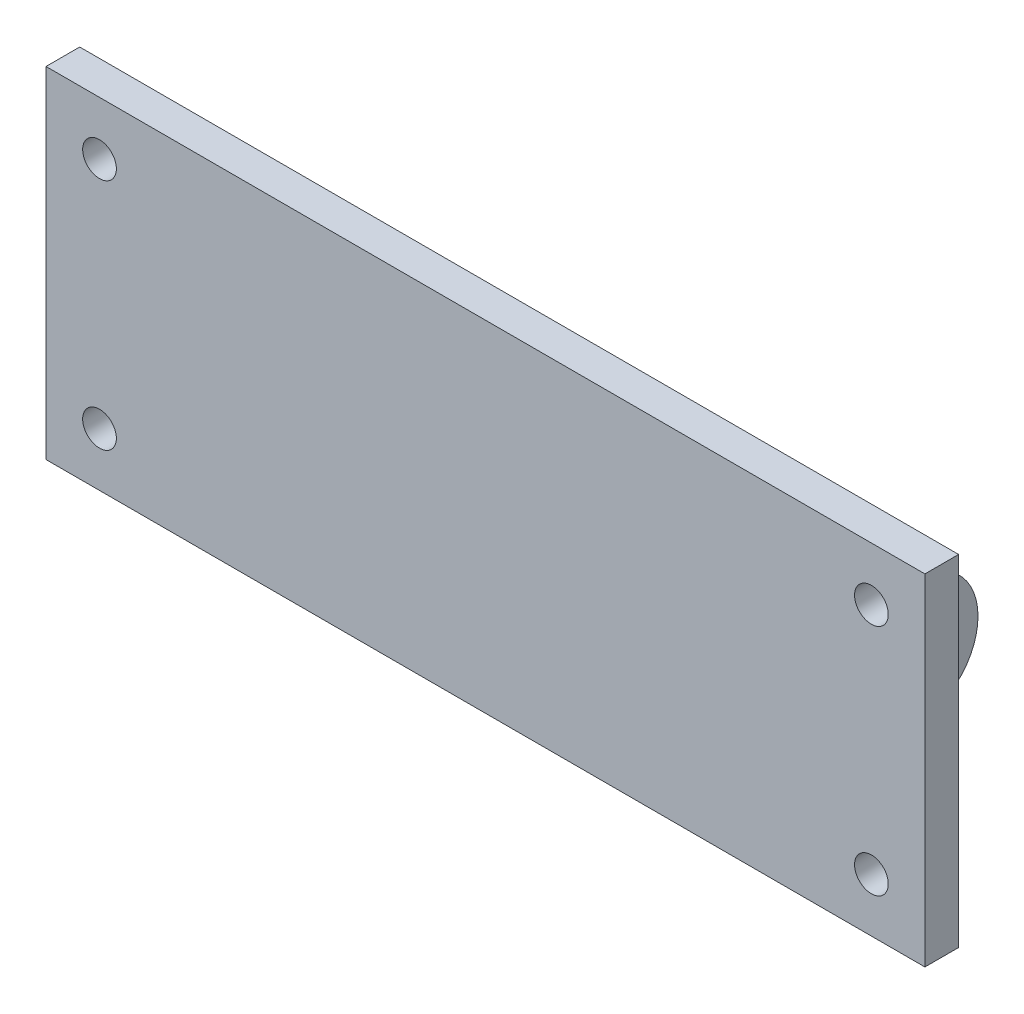
SolidWorks part; units mm, degrees
ref_plane "Front Plane" through (0, 0, 0) normal (0, 0, 1) x (1, 0, 0)
ref_plane "Top Plane" through (0, 0, 0) normal (0, 1, 0) x (1, 0, 0)
ref_plane "Right Plane" through (0, 0, 0) normal (1, 0, 0) x (0, 0, -1)
sketch "Sketch1" plane through (0, 0, 0) normal (0, 0, 1) x (1, 0, 0)
  line L0 (-57.0556, -260.4467) -> (-37.0556, -260.4467)
  line L5 (-57.0556, -260.4467) -> (-57.0556, -290.4467)
  line L6 (-57.0556, -290.4467) -> (-37.0556, -290.4467)
  line L11 (-37.0556, -260.4467) -> (-37.0556, -290.4467)
  line L12 (-57.0556, -260.4467) -> (-37.0556, -290.4467) construction
  line L13 (-57.0556, -290.4467) -> (-37.0556, -260.4467) construction
  line L14 (80.7444, -260.4467) -> (100.7444, -260.4467)
  line L15 (80.7444, -260.4467) -> (80.7444, -290.4467)
  line L16 (80.7444, -290.4467) -> (100.7444, -290.4467)
  line L17 (100.7444, -260.4467) -> (100.7444, -290.4467)
  line L18 (80.7444, -260.4467) -> (100.7444, -290.4467) construction
  line L19 (80.7444, -290.4467) -> (100.7444, -260.4467) construction
  line L21 (126.1444, -235.0467) -> (-82.4556, -235.0467)
  line L22 (126.1444, -235.0467) -> (126.1444, -315.8467)
  line L23 (126.1444, -315.8467) -> (-82.4556, -315.8467)
  line L24 (-82.4556, -235.0467) -> (-82.4556, -315.8467)
  line L25 (126.1444, -235.0467) -> (-82.4556, -315.8467) construction
  line L26 (126.1444, -315.8467) -> (-82.4556, -235.0467) construction
  circle A0 centre (113.4444, -247.7467) radius 4
  circle A1 centre (-69.7556, -303.1467) radius 4
  circle A3 centre (113.4444, -303.1467) radius 4
  circle A4 centre (-69.7556, -247.7467) radius 4
  point P0 (-47.0556, -275.4467)
  point P5 (90.7444, -275.4467)
  point P10 (21.8444, -275.4467)
  dimension "D7" = 8
  dimension "D8" = 12.7
  dimension "D10" = 12.7
  dimension "D11" = 25.4
  dimension "D14" = 8
  dimension "D15" = 12.7
  dimension "D17" = 8
  dimension "D18" = 8
  dimension "D19" = 12.7
  dimension "D20" = 12.7
  dimension "D21" = 12.7
  dimension "D22" = 12.7
  dimension "D1" = 20
  dimension "D2" = 30
  dimension "D3" = 20
  dimension "D4" = 30
  dimension "D5" = 117.8
  dimension "D6" = 0
  dimension "D9" = 25.4
  dimension "D12" = 25.4
  dimension "D13" = 25.4
  dimension "D16" = 12.7
extrude "Boss-Extrude1" add sketch "Sketch1" along normal blind 8 contours L17 L14 L15 L16 | L11 L0 L5 L6 | L21 L24 L23 L22 A3 A4 A1 A0 L14 L17 L16 L15 L0 L11 L6 L5 region at (-47.0556, -275.4467, 0) region at (90.7444, -275.4467, 0) region at (21.8444, -275.4467, 0)
extrude "Boss-Extrude2" add sketch "Sketch1<3>" against normal blind 30 contours L17 L14 L15 L16 | L11 L0 L5 L6 region at (-47.0556, -275.4467, 0) region at (90.7444, -275.4467, 0)
sketch "Sketch1<3>" plane through (0, 0, 0) normal (0, 0, 1) x (1, 0, 0) same geometry as "Sketch1"
fillet "Fillet1" radius 5 4 edges at (-47.0556, -260.4467, 0) (-47.0556, -290.4467, 0) (90.7444, -290.4467, 0) (90.7444, -260.4467, 0)
fillet "Fillet2" radius 15 4 edges at (90.7444, -260.4467, -30) (90.7444, -290.4467, -30) (-47.0556, -290.4467, -30) (-47.0556, -260.4467, -30)
sketch "Sketch2" plane through (100.7444, 0, 0) normal (1, 0, 0) x (0, 0, -1)
  line L0 (0, -235.0467) -> (0, -315.8467) construction
  line L1 (15, -260.4467) -> (5, -260.4467) construction
  circle A0 centre (15, -275.4467) radius 5
  dimension "D1" = 10
  dimension "D2" = 15
  dimension "D3" = 15
extrude "Cut-Extrude1" cut sketch "Sketch2" against normal through all
